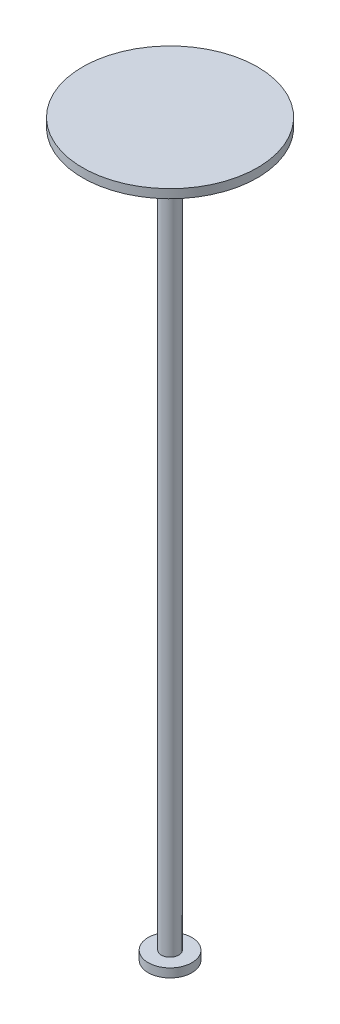
SolidWorks part; units mm, degrees
ref_plane "Front Plane" through (0, 0, 0) normal (0, 0, 1) x (1, 0, 0)
ref_plane "Top Plane" through (0, 0, 0) normal (0, 1, 0) x (1, 0, 0)
ref_plane "Right Plane" through (0, 0, 0) normal (1, 0, 0) x (0, 0, -1)
sketch "Sketch1" plane through (0, 0, 0) normal (0, 0, 1) x (1, 0, 0)
  line L0 (0, 0) -> (0, 207.1568)
  line L1 (0, 207.1568) -> (25.4, 207.1568)
  line L3 (25.4, 207.1568) -> (25.4, 204.6168)
  line L4 (2.54, -2.3932) -> (2.54, 204.6168)
  line L5 (2.54, 204.6168) -> (25.4, 204.6168)
  line L9 (2.54, -2.3932) -> (6.35, -2.3932)
  line L10 (0, 0) -> (0, -4.9332)
  line L11 (0, -4.9332) -> (6.35, -4.9332)
  line L12 (6.35, -2.3932) -> (6.35, -4.9332)
  dimension "D1" = 6.35
  dimension "D2" = 25.4
  dimension "D3" = 2.54
  dimension "D4" = 2.54
  dimension "D5" = 207.01
  dimension "D6" = 2.54
revolve "Revolve1" add sketch "Sketch1" angle 360 about L0
